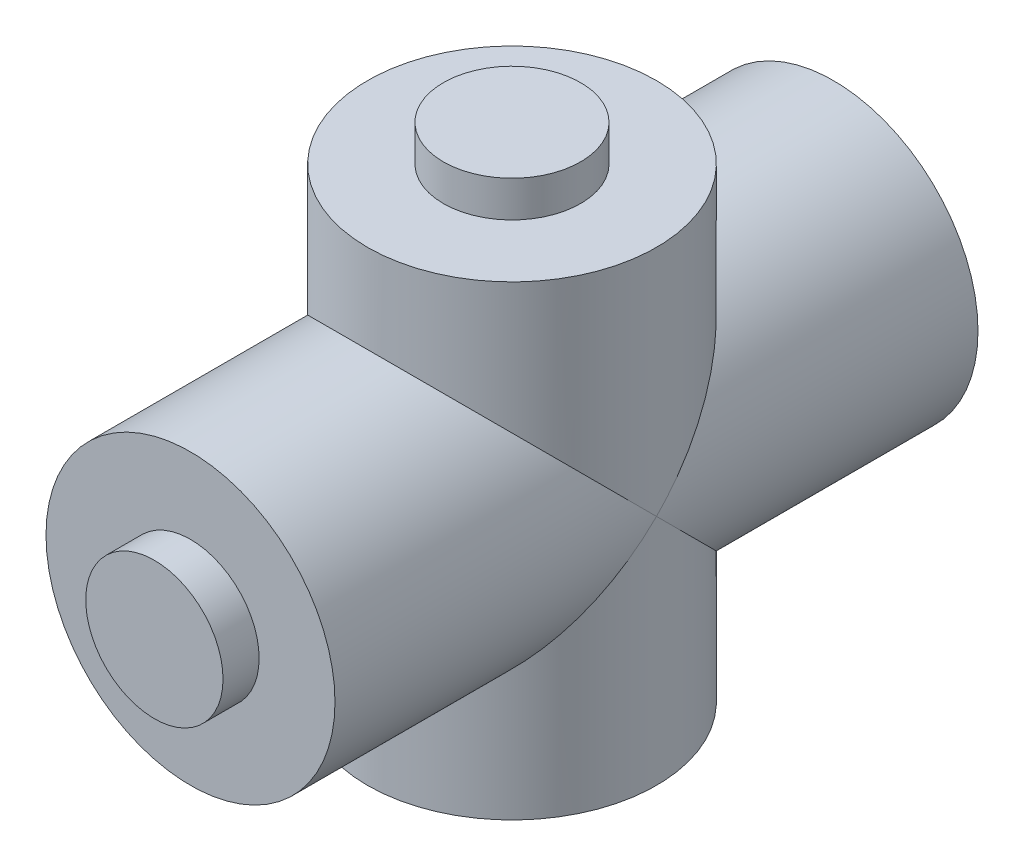
SolidWorks part; units mm, degrees
ref_plane "前视基准面" through (0, 0, 0) normal (0, 0, 1) x (1, 0, 0)
ref_plane "上视基准面" through (0, 0, 0) normal (0, 1, 0) x (1, 0, 0)
ref_plane "右视基准面" through (0, 0, 0) normal (1, 0, 0) x (0, 0, -1)
sketch "草图1" plane through (0, 0, 0) normal (0, 0, 1) x (1, 0, 0)
  circle A0 centre (0, 0) radius 4
extrude "凸台-拉伸1" add sketch "草图1" along normal blind 17.8
sketch "草图2" plane through (0, 0, 17.8) normal (0, 0, 1) x (1, 0, 0)
  circle A0 centre (0, 0) radius 1.9
extrude "凸台-拉伸2" add sketch "草图2" along normal blind 1
sketch "草图3" plane through (0, 0, 0) normal (0, 0, -1) x (-1, 0, 0)
  circle A0 centre (0, 0) radius 1.9
extrude "凸台-拉伸3" add sketch "草图3" along normal blind 1
sketch "草图4" plane through (0, 0, 0) normal (0, 1, 0) x (1, 0, 0)
  circle A0 centre (0, -8.9) radius 4
extrude "凸台-拉伸4" add sketch "草图4" along normal blind 6.45 and the other way blind 6.45
sketch "草图5" plane through (0, -6.45, 0) normal (0, -1, 0) x (-1, 0, 0)
  circle A0 centre (0, -8.9) radius 1.9
extrude "凸台-拉伸5" add sketch "草图5" along normal blind 1
sketch "草图6" plane through (0, 6.45, 0) normal (0, 1, 0) x (1, 0, 0)
  circle A0 centre (0, -8.9) radius 1.9
extrude "凸台-拉伸6" add sketch "草图6" along normal blind 1
